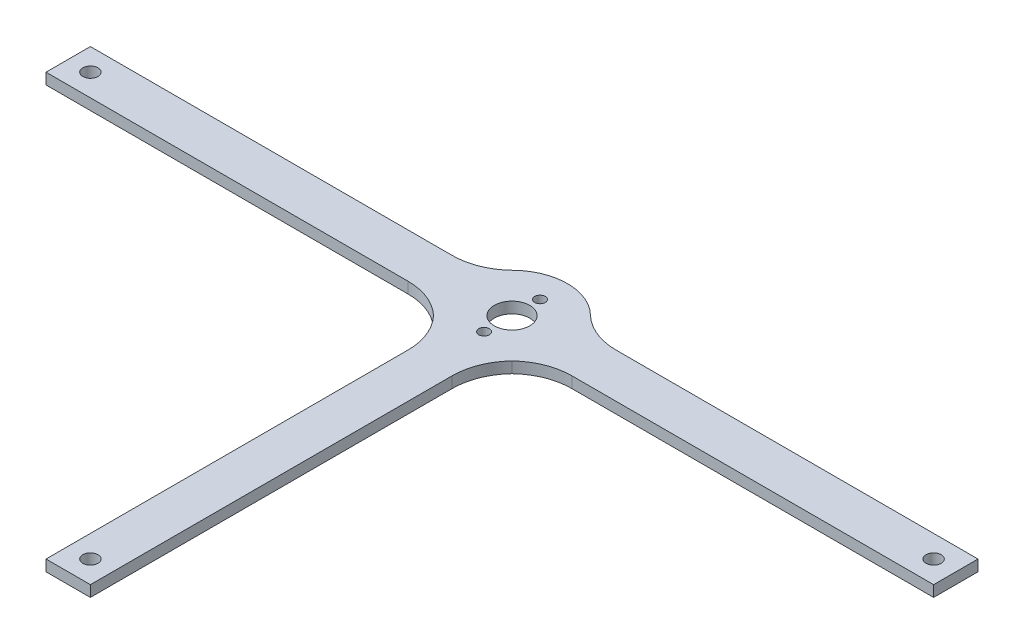
SolidWorks part; units mm, degrees
ref_plane "Front Plane" through (0, 0, 0) normal (0, 0, 1) x (1, 0, 0)
ref_plane "Top Plane" through (0, 0, 0) normal (0, 1, 0) x (1, 0, 0)
ref_plane "Right Plane" through (0, 0, 0) normal (1, 0, 0) x (0, 0, -1)
sketch "Sketch1" plane through (0, 0, 0) normal (0, 1, 0) x (1, 0, 0)
  line L0 (-14.5497, 6.35) -> (-127, 6.35)
  line L1 (127, -6.35) -> (14.5497, -6.35)
  line L2 (127, -6.35) -> (127, 6.35)
  line L3 (127, 6.35) -> (14.5497, 6.35)
  line L4 (-127, -6.35) -> (-127, 6.35)
  line L9 (-6.35, -127) -> (6.35, -127)
  line L12 (6.35, -14.5497) -> (6.35, -127)
  line L13 (-6.35, -14.5497) -> (-6.35, -127)
  line L14 (-14.5497, -6.35) -> (-127, -6.35)
  arc A2 (14.5497, 6.35) -> (-14.5497, 6.35) centre (0, 0) ccw
  arc A3 (-14.5497, -6.35) -> (-6.35, -14.5497) centre (0, 0) ccw
  arc A4 (6.35, -14.5497) -> (14.5497, -6.35) centre (0, 0) ccw
  point P0 (0, 0)
  point P11 (0, -127)
  dimension "D5" = 31.75
  dimension "D1" = 254
  dimension "D2" = 12.7
  dimension "D3" = 127
  dimension "D4" = 12.7
  dimension "D6" = 127
sketch "Screw holes" plane through (0, 0, 0) normal (0, 1, 0) x (1, 0, 0)
  circle A0 centre (0, 8) radius 1.5133
  circle A1 centre (0, -8) radius 1.5133
  circle A2 centre (0, 0) radius 5.08
  dimension "D1" = 16
  dimension "D3" = 3.0266
  dimension "D4" = 10.16
  dimension "D2" = 8
extrude "Boss-Extrude1" add sketch "Sketch1" along normal blind 3.175
extrude "Cut-Extrude1" cut sketch "Screw holes" along normal through all
fillet "Fillet1" radius 17.78 6 edges at (14.5497, 1.5875, 6.35) (14.5497, 1.5875, -6.35) (-14.5497, 1.5875, -6.35) (-6.35, 1.5875, 14.5497) (-14.5497, 1.5875, 6.35) (6.35, 1.5875, 14.5497)
sketch "Sketch2" plane through (0, 3.175, 0) normal (0, 1, 0) x (1, 0, 0)
  line L0 (-127, 6.35) -> (-127, -6.35) construction
  line L1 (-23.4607, 6.35) -> (-127, 6.35) construction
  circle A0 centre (-120.65, 0) radius 2.159
  circle A2 centre (120.65, 0) radius 2.159
  circle A3 centre (0, -120.65) radius 2.159
  circle A4 centre (0, 120.65) radius 2.159 [skipped]
  point P15 (0, 0)
  dimension "D1" = 4.318
  dimension "D2" = 6.35
  dimension "D3" = 6.35
  dimension "D4" = 4
extrude "Cut-Extrude2" cut sketch "Sketch2" against normal through all
